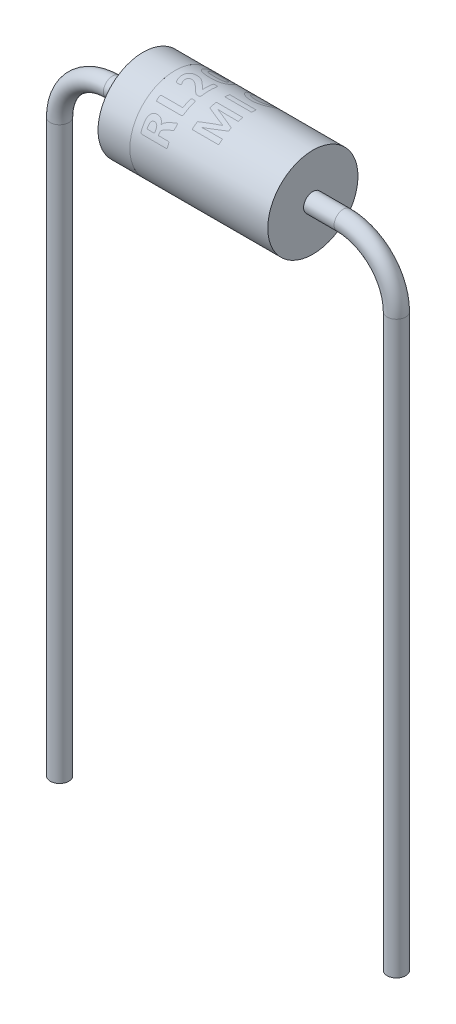
SolidWorks part; units mm, degrees
other "Diode"
other "Cathode Silver Band"
other "Wire"
ref_plane "Front Plane" through (0, 0, 0) normal (0, 0, 1) x (1, 0, 0)
ref_plane "Top Plane" through (0, 0, 0) normal (0, 1, 0) x (1, 0, 0)
ref_plane "Right Plane" through (0, 0, 0) normal (1, 0, 0) x (0, 0, -1)
sketch "Sketch1" plane through (0, 0, 0) normal (1, 0, 0) x (0, 0, -1)
  circle A0 centre (0, 0) radius 1.7
  circle A1 centre (0, 0) radius 0.35
  dimension "D1" = 3.4
  dimension "D2" = 0.7
extrude "Boss-Extrude1" add sketch "Sketch1" along normal mid plane 6.4
sketch "Sketch2" plane through (-3.2, 0, 0) normal (-1, 0, 0) x (0, 0, 1)
  circle A1 centre (0, 0) radius 1.7 construction
  circle A2 centre (0, 0) radius 1.69
  circle A3 centre (0, 0) radius 1.69
  circle A4 centre (0, 0) radius 1.7
  dimension "D1" = 0.01
extrude "Cut-Extrude1" cut sketch "Sketch2" against normal blind 1.2
sketch "Sketch3" plane through (-2, 0, 0) normal (-1, 0, 0) x (0, 0, 1)
  circle A0 centre (0, 0) radius 1.69 construction
  circle A1 centre (0, 0) radius 1.69
  circle A2 centre (0, 0) radius 1.7 construction
  circle A3 centre (0, 0) radius 1.7
extrude "Boss-Extrude2" add sketch "Sketch3" along normal up to surface (1.2 mm away) separate body up to face at (-3.2, 0, -0.35)
ref_plane "Plane1" through (0, 5, 0) normal (0, 1, 0) x (1, 0, 0)
sketch "Sketch4" plane through (0, 5, 0) normal (0, 1, 0) x (1, 0, 0)
  line L0 (-0.7, 7.5) -> (-0.7, -7.5) construction
  line L1 (-0.7, 0) -> (-3.2, 0) construction
  line L2 (-3.2, 1.7) -> (-3.2, -1.7) construction
  line L4 (-0.7, 0) -> (0.8, 0) construction
  line L5 (0.8, 7.5) -> (0.8, -7.5) construction
  text T0 "RL207" font "Calibri" height 1
  text T1 "MIC" font "Corbel" height 1
  dimension "D1" = 2.5
  dimension "D2" = 15
  dimension "D3" = 1.5
wrap "Wrap1" sketch "Sketch4" wrap type scribe source sketch "Sketch4" face at (3.2, 0, -1.7)
sketch "Sketch5" plane through (0, 0, 0) normal (0, 0, 1) x (1, 0, 0)
  line L0 (0, 0) -> (-4.35, 0)
  line L1 (-6.35, -2) -> (-6.35, -23.5084)
  line L2 (0, 0) -> (4.35, 0)
  line L3 (6.35, -2) -> (6.35, -23.5084)
  arc A0 (-4.35, 0) -> (-6.35, -2) centre (-4.35, -2) ccw
  arc A1 (4.35, 0) -> (6.35, -2) centre (4.35, -2) cw
  dimension "D2" = 2
  dimension "D3" = 58
  dimension "D1" = 12.7
sketch "Sketch6" plane through (0, 0, 0) normal (1, 0, 0) x (0, 0, -1)
  circle A0 centre (0, 0) radius 0.35
  dimension "D1" = 0.7
sweep "Sweep1" add profiles "Sketch6" path "Sketch5"
